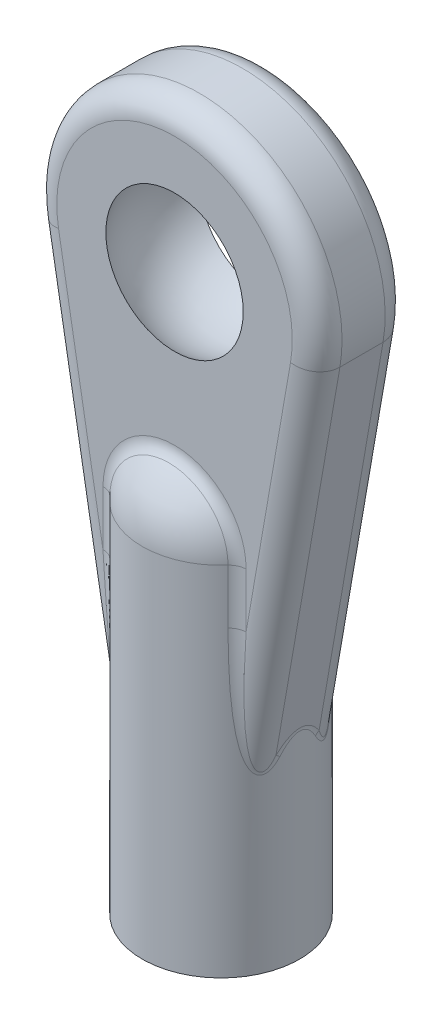
SolidWorks part; units mm, degrees
ref_plane "Front Plane" through (0, 0, 0) normal (0, 0, 1) x (1, 0, 0)
ref_plane "Top Plane" through (0, 0, 0) normal (0, 1, 0) x (1, 0, 0)
ref_plane "Right Plane" through (0, 0, 0) normal (1, 0, 0) x (0, 0, -1)
sketch "Sketch1" plane through (0, 0, 0) normal (0, 0, 1) x (1, 0, 0)
  line L0 (0, 0) -> (0, -17.45) construction
  line L1 (0, -17.45) -> (-2.375, -17.45) construction
  line L2 (-2.375, -17.45) -> (-2.375, -11.45) construction
  line L3 (-2.375, -11.45) -> (2.375, -11.45) construction
  line L4 (2.375, -11.45) -> (2.375, -17.45) construction
  line L5 (2.375, -17.45) -> (0, -17.45) construction
  line L6 (0, 0) -> (0, 4.3) construction
  line L7 (2.375, -11.45) -> (4.2365, -0.7361)
  line L8 (-4.2365, -0.7361) -> (-2.375, -11.45)
  line L9 (-2.375, -11.45) -> (2.375, -11.45) construction
  line L10 (-2.375, -11.45) -> (-2.2013, -12.45)
  line L11 (-2.2013, -12.45) -> (2.2013, -12.45)
  line L12 (2.2013, -12.45) -> (2.375, -11.45)
  arc A0 (4.2365, -0.7361) -> (-4.2365, -0.7361) centre (0, 0) ccw
  dimension "D1" = 8.6
  dimension "D2" = 4.75
  dimension "D3" = 21.75
  dimension "D4" = 6
  dimension "D5" = 1
extrude "Boss-Extrude1" add sketch "Sketch1" along normal mid plane 2.8
sketch "Sketch2" plane through (0, 0, 0) normal (0, 0, 1) x (1, 0, 0)
  line L0 (0, 0) -> (0, -17.45) construction
  line L1 (0, -17.45) -> (-2.375, -17.45)
  line L2 (-2.375, -17.45) -> (-2.375, -11.45)
  line L3 (-2.375, -11.45) -> (-2.375, -6.675)
  line L4 (0, -6.675) -> (0, -4.3)
  line L5 (0, -6.675) -> (0, -17.45)
  line L6 (2.375, -17.45) -> (0, -17.45) construction
  circle A0 centre (0, 0) radius 4.3 construction
  arc A1 (4.2365, -0.7361) -> (-4.2365, -0.7361) centre (0, 0) ccw construction
  arc A2 (0, -4.3) -> (-2.375, -6.675) centre (0, -6.675) ccw
  point P15 (0, 0)
  point P16 (-2.375, -11.45)
revolve "Revolve1" add sketch "Sketch2" angle 360 about L0
sketch "Sketch3" plane through (0, 0, 0) normal (1, 0, 0) x (0, 0, -1)
  line L0 (0, -2.5) -> (0, 2.5)
  arc A0 (0, 2.5) -> (0, -2.5) centre (0, 0) ccw
  dimension "D1" = 2.5
revolve "Cut-Revolve1" cut sketch "Sketch3" angle 360 about L0
fillet "Fillet1" radius 0.75 6 edges at (3.2189, -6.593, -1.4) (0, 4.3, -1.4) (3.2189, -6.593, 1.4) (0, 4.3, 1.4) (-3.2189, -6.593, -1.4) (-3.2189, -6.593, 1.4)
fillet "Fillet2" radius 0.5 12 edges at (2.1464, -12.2064, -1.0167) (1.9185, -8.1856, -1.4) (0, -4.7565, -1.4) (-2.1689, -12.2236, -0.9678) (2.1689, -12.2236, 0.9678) (1.9185, -8.1856, 1.4) (0, -4.7565, 1.4) (-2.1464, -12.2064, 1.0167) (-1.9185, -8.1856, -1.4) (-1.9185, -8.1856, 1.4) (2.375, -11.45, 0) (-2.375, -11.45, 0)
hole_wizard "M3 Tapped Hole1" positions "Sketch4" profile "Sketch5" tap size "M3" standard "DIN"
sketch "Sketch4" plane through (0, -17.45, 0) normal (0, -1, 0) x (-1, 0, 0)
  point P0 (0, 0)
cosmetic thread "Hole Thread1" parameters "D2"=3
sketch "Sketch5" plane through (0, -17.45, 0) normal (1, 0, 0) x (0, 0, -1)
  line L0 (0, 0) -> (0, 9.3871)
  line L1 (0, 9.3871) -> (1.25, 8.636)
  line L2 (1.25, 8.636) -> (1.25, 0)
  line L5 (1.25, 0) -> (0, 0)
  line L10 (0, 9.3871) -> (-1.25, 8.636) construction
  line L11 (0, -6.35) -> (0, 107.95) construction
  dimension "Tap Drill Dia." = 2.5
  dimension "Tap Drill Depth" = 8.636
  dimension "Drill Angle" = 118
